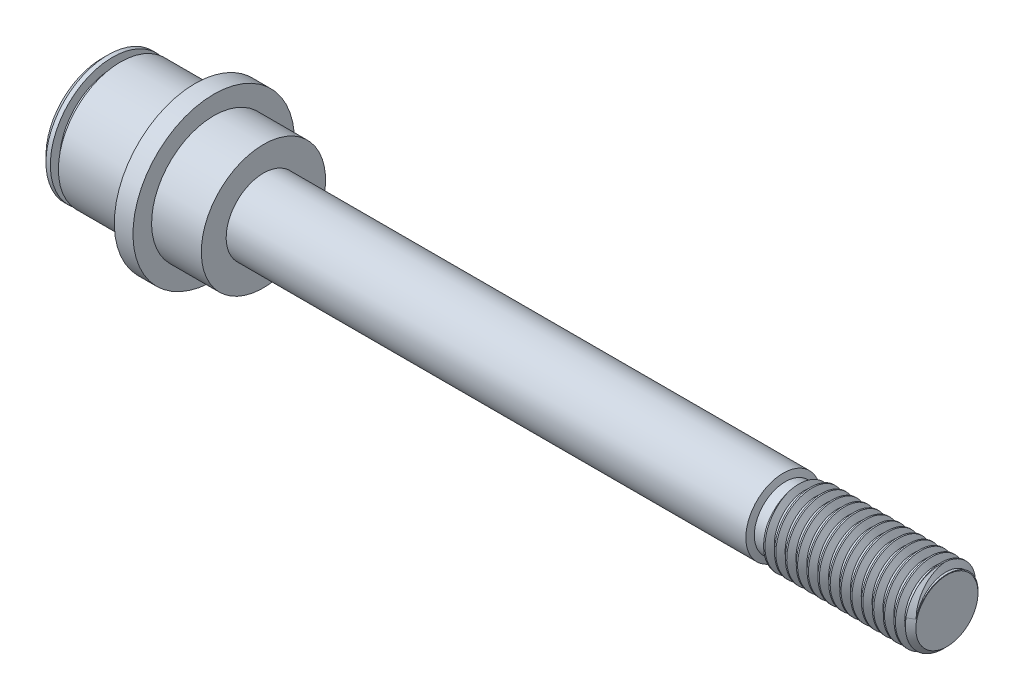
SolidWorks part; units mm, degrees
ref_plane "Front Plane" through (0, 0, 0) normal (0, 0, 1) x (1, 0, 0)
ref_plane "Top Plane" through (0, 0, 0) normal (0, 1, 0) x (1, 0, 0)
ref_plane "Right Plane" through (0, 0, 0) normal (1, 0, 0) x (0, 0, -1)
sketch "Sketch1" plane through (0, 0, 0) normal (0, 0, 1) x (1, 0, 0)
  line L0 (0, 0) -> (0, 10)
  line L1 (0, 10) -> (15, 10)
  line L2 (15, 10) -> (15, 13)
  line L3 (15, 13) -> (18, 13)
  line L4 (18, 13) -> (18, 10)
  line L5 (18, 10) -> (26, 10)
  line L6 (26, 10) -> (26, 6)
  line L7 (26, 6) -> (136, 6)
  line L8 (136, 6) -> (136, 0)
  line L9 (136, 0) -> (0, 0)
  dimension "D1" = 10
  dimension "D2" = 15
  dimension "D3" = 3
  dimension "D4" = 8
  dimension "D5" = 6
  dimension "D6" = 13
  dimension "D7" = 110
revolve "Revolve1" add sketch "Sketch1" angle 360 about L9
chamfer "Chamfer1" distance 1 angle 45 2 edges at (136, 6, 0) (0, 10, 0)
thread "Thread2" pitch 1.75 method cut profile "Thread Profile2" start angle 0, offset 1, length 25, pitch 1.75, diameter 12
ref_plane "Plane2" through (137, 0, 6) normal (0, -1, 0) x (0, 0, 1)
sketch "Thread Profile2" plane through (137, 0, 6) normal (0, -1, 0) x (0, 0, 1)
  line L0 (0, 0) -> (0, 1.75) construction
  line L11 (0, 0) -> (0, 1.5312)
  line L12 (0, 1.5312) -> (-0.9472, 0.9844)
  line L13 (-0.9472, 0.9844) -> (-0.9472, 0.5469)
  line L15 (-0.9472, 0.5469) -> (0, 0)
  line L17 (-0.9472, 0.7656) -> (0, 0.7656) construction
  point P2 (0, 0)
  dimension "Pitch" = 1.75
  dimension "Profile_Angle" = 60
  dimension "Profile_Land" = 0.4375
  dimension "Profile_Height" = 0.9472
sketch "Sketch15" plane through (0, 0, 0) normal (0, 0, 1) x (1, 0, 0)
  line L0 (15, 13) -> (15, -13) construction
  line L1 (1.7, 11.5) -> (3, 11.5)
  line L2 (1.7, 11.5) -> (1.7, 8.5)
  line L3 (1.7, 8.5) -> (3, 8.5)
  line L4 (3, 11.5) -> (3, 8.5)
  line L5 (0, 0) -> (20.0335, 0) construction
  dimension "D1" = 1.3
  dimension "D2" = 8.5
  dimension "D3" = 12
  dimension "D4" = 3
revolve "Cut-Revolve1" cut sketch "Sketch15" angle 360 about L5
sketch "Sketch16" plane through (0, 0, 0) normal (0, 0, 1) x (1, 0, 0)
  line L0 (111, 5) -> (111, 6.5) construction
  line L1 (109.454, 6.5) -> (112.546, 6.5)
  line L2 (109.454, 6.5) -> (110, 5)
  line L3 (110, 5) -> (112, 5)
  line L4 (112.546, 6.5) -> (112, 5)
  line L5 (0, 0) -> (146.642, 0) construction
  line L6 (136, -5) -> (136, 5) construction
  dimension "D1" = 2
  dimension "D2" = 40
  dimension "D3" = 24
  dimension "D4" = 5
  dimension "D5" = 6.5
revolve "Cut-Revolve3" cut sketch "Sketch16" angle 360 about L5
